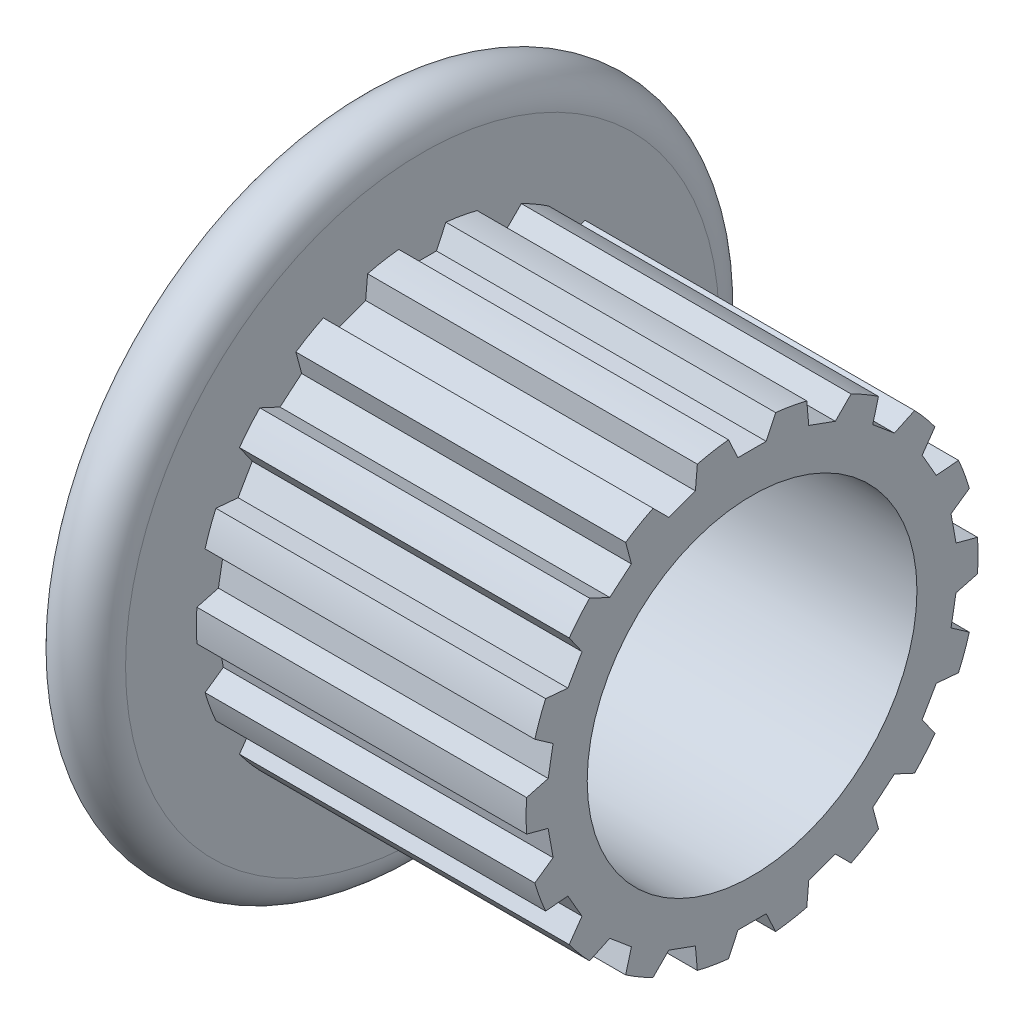
SolidWorks part; units mm, degrees
ref_plane "Front Plane" through (0, 0, 0) normal (0, 0, 1) x (1, 0, 0)
ref_plane "Top Plane" through (0, 0, 0) normal (0, 1, 0) x (1, 0, 0)
ref_plane "Right Plane" through (0, 0, 0) normal (1, 0, 0) x (0, 0, -1)
sketch "Sketch2" plane through (0, 0, 0) normal (1, 0, 0) x (0, 0, -1)
  line L3 (0, 0) -> (0, 4.9745) construction
  line L6 (0, -5.4825) -> (0, -5.8) construction
  line L7 (-0.5715, 5.4526) -> (-0.343, 4.9627)
  line L8 (0.5715, 5.4526) -> (0.343, 4.9627)
  line L9 (-0.5715, 5.4526) -> (-0.6423, 5.6046)
  line L10 (0.5715, 5.4526) -> (0.6423, 5.6046)
  line L12 (-0.343, 4.9627) -> (0.343, 4.9627)
  line L14 (0, 5.4825) -> (0, 5.8) construction
  line L15 (0, 0) -> (0, -1.143) construction
  circle A0 centre (0, 0) radius 5.8 construction
  circle A1 centre (0, 0) radius 4.9745 construction
  circle A2 centre (0, 0) radius 5.4825 construction
  arc A7 (0.6423, 5.6046) -> (-0.6423, 5.6046) centre (0, 0) ccw
  point P5 (0, 5.6413)
  dimension "D3" = 0.3175
  dimension "D1" = 50
sketch "Sketch1" plane through (0, 0, 0) normal (0, 0, 1) x (1, 0, 0)
  line L0 (-1.6, 0) -> (9.6, 0) construction
  line L1 (-1.6, 4) -> (8, 4)
  line L3 (9.6, 4) -> (8, 4) construction
  line L4 (8, 4) -> (8, 5.55)
  line L5 (8, 5.55) -> (0, 5.55)
  line L6 (0, 5.55) -> (0, 7.2)
  line L7 (-1.6, 7.2) -> (-1.6, 4)
  line L8 (9.6, 4) -> (9.6, 5) construction
  line L9 (9.6, 5) -> (8, 5) construction
  arc A0 (0, 7.2) -> (-1.6, 7.2) centre (-0.8, 7.2) ccw
  dimension "D1" = 5
  dimension "For Shaft Dia." = 8
  dimension "D2" = 1.6
  dimension "Overall Width" = 11.2
  dimension "Inside Width" = 8
  dimension "OD" = 16
  dimension "Flange Dia." = 11.1
revolve "Revolve1" add sketch "Sketch1" angle 360 mid plane about L0
sketch "Sketch7" plane through (0, 0, 0) normal (0, 0, 1) x (1, 0, 0)
  line L0 (8, 4) -> (8, 5.55) construction
  line L1 (9.6, 5) -> (8, 5) construction
  line L2 (9.6, 4) -> (9.6, 5) construction
  line L3 (9.6, 4) -> (8, 4) construction
  line L4 (8, 4) -> (8, 5)
  line L5 (9.6, 5) -> (8, 5)
  line L6 (9.6, 4) -> (9.6, 5)
  line L7 (9.6, 4) -> (8, 4)
revolve "Revolve2" [suppressed] add sketch "Sketch7" angle 360 about L0
sketch "Sketch8" plane through (0, 0, 0) normal (0, 0, 1) x (1, 0, 0)
  line L0 (8, -5.55) -> (8, 5.55) construction
  line L1 (8, 8.75) -> (4.35, 8.75)
  line L2 (8, 8.75) -> (8, 1.55)
  line L3 (8, 1.55) -> (4.35, 1.55)
  line L4 (4.35, 8.75) -> (4.35, 1.55)
  line L6 (-1.6, 8.75) -> (2.05, 8.75)
  line L7 (-1.6, 8.75) -> (-1.6, 1.55)
  line L8 (-1.6, 1.55) -> (2.05, 1.55)
  line L9 (2.05, 8.75) -> (2.05, 1.55)
  line L10 (-1.6, 7.2) -> (-1.6, -7.2) construction
  line L11 (-1.6, 0) -> (8, 0) construction
  line L12 (2.05, 8.75) -> (4.35, 8.75) construction
  line L13 (3.2, 8.75) -> (3.2, 0) construction
  line L14 (8, 5.55) -> (0, 5.55) construction
  dimension "D1" = 2.3
  dimension "D2" = 17.5
  dimension "D3" = 4
revolve "Cut-Revolve1" [suppressed] cut sketch "Sketch8" angle 360 about L11
sketch "Sketch4" plane through (0, 0, 0) normal (1, 0, 0) x (0, 0, -1)
  circle A0 centre (0, 0) radius 5.4825
  circle A1 centre (0, 0) radius 5.4825 construction
  circle A2 centre (0, 0) radius 5.8
  circle A4 centre (0, 0) radius 5.8 construction
extrude "Cut-Extrude2" cut sketch "Sketch4" along normal up to surface (8 mm away) up to face at (8, 0, 5.55)
sketch "Sketch3" plane through (0, 0, 0) normal (1, 0, 0) x (0, 0, -1)
  line L2 (-0.5715, 5.4526) -> (-0.343, 4.9627) construction
  line L3 (-0.343, 4.9627) -> (0.343, 4.9627) construction
  line L4 (0.5715, 5.4526) -> (0.343, 4.9627) construction
  line L5 (-0.6423, 5.6046) -> (-0.343, 4.9627)
  line L6 (-0.343, 4.9627) -> (0.343, 4.9627)
  line L7 (0.6423, 5.6046) -> (0.343, 4.9627)
  arc A1 (0.6423, 5.6046) -> (-0.6423, 5.6046) centre (0, 0) ccw construction
  arc A2 (0.6423, 5.6046) -> (-0.6423, 5.6046) centre (0, 0) ccw
extrude "Cut-Extrude1" cut sketch "Sketch3" along normal up to surface (8 mm away) up to face at (8, 0, 5.4825)
pattern_circular "CirPattern1" count 18 over 360 about axis through (-1.6, 0, 0) along (-1, 0, 0) of "Cut-Extrude1"
sketch "Sketch5" plane through (0, 0, 0) normal (0, 0, 1) x (1, 0, 0)
  point P0 (8, 0)
ref_axis "Center Axis 1" through (8, 0, 0) along (-1, 0, 0)
ref_plane "Contact Plane 1" through (8, 0, 0) normal (1, 0, 0) x (0, 0, -1)
ref_plane "Contact Plane 2" through (-1.6, 0, 0) normal (-1, 0, 0) x (0, 0, 1)
equation "\"D3@Sketch2\" = (\"hs@Sketch2\"-\"ht@Sketch2\")/2"
